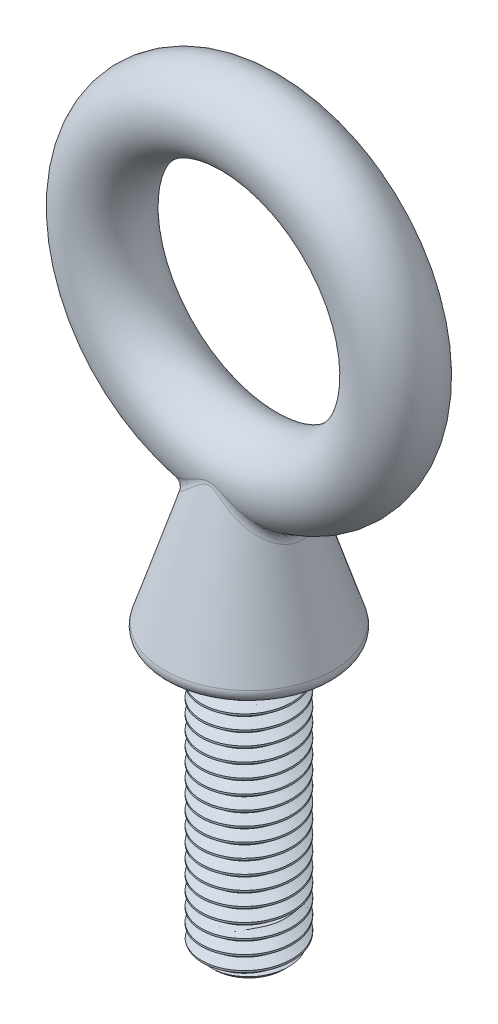
SolidWorks part; units mm, degrees
ref_plane "Front Plane" through (0, 0, 0) normal (0, 0, 1) x (1, 0, 0)
ref_plane "Top Plane" through (0, 0, 0) normal (0, 1, 0) x (1, 0, 0)
ref_plane "Right Plane" through (0, 0, 0) normal (1, 0, 0) x (0, 0, -1)
sketch "Sketch1" plane through (0, 0, 0) normal (0, 0, 1) x (1, 0, 0)
  line L0 (0, -26.1937) -> (0, -80.1688) construction
  line L1 (-6.35, -80.1688) -> (6.35, -80.1688) construction
  line L3 (0, -26.1937) -> (0, -15.0812) construction
  line L4 (-11.9062, -42.0687) -> (11.9063, -42.0687) construction
  circle A0 centre (0, 0) radius 26.1937 construction
  circle A1 centre (0, 20.6375) radius 5.5562 construction
  circle A2 centre (0, 0) radius 15.0813 construction
  point P7 (0, -26.1937)
  point P9 (0, -42.0687)
  point P10 (0, 26.1937)
  point P11 (0, 15.0812)
  point P14 (0, -80.1688)
  point P19 (0, -20.6375)
  point P21 (0, -42.0687)
sketch "Sketch2" plane through (0, 0, 0) normal (0, 1, 0) x (1, 0, 0)
  circle A0 centre (0, 0) radius 6.35
extrude "Boss-Extrude1" add sketch "Sketch2" against normal up to vertex (80.1688 mm away) from vertex at -42.0688 starting at point (0, -42.0687, 0)
sketch "Sketch3" plane through (0, -80.1688, 0) normal (0, -1, 0) x (1, 0, 0)
  circle A1 centre (0, 0) radius 6.35
  circle A2 centre (0, 0) radius 6.35
  point P0 (6.35, 0)
  point P1 (0, -6.35)
  dimension "D1" = 0
curve "Helix/Spiral1" pitch 1.9538 height 40.0538 turns 20.5 parameters "Pitch"=1.9538
sketch "Sketch4" plane through (0, 0, 0) normal (0, 0, 1) x (1, 0, 0)
  line L0 (6.5615, -80.0466) -> (6.5615, -82.0005) construction
  line L1 (6.5615, -82.0005) -> (4.8694, -81.0236) construction
  line L2 (4.8694, -81.0236) -> (6.5615, -80.0466) construction
  line L3 (5.0809, -80.9014) -> (5.0809, -81.1457) construction
  line L4 (6.35, -80.1688) -> (6.35, -81.8784) construction
  line L5 (4.8694, -81.0236) -> (5.0809, -81.0236) construction
  line L6 (6.35, -81.0236) -> (6.5615, -81.0236) construction
  line L7 (6.4558, -80.1077) -> (5.0809, -80.9014)
  line L8 (5.0809, -80.9014) -> (5.0809, -81.1457)
  line L9 (5.0809, -81.1457) -> (6.4558, -81.9394)
  line L10 (6.4558, -81.9394) -> (6.4558, -80.1077)
  point P13 (6.4558, -81.0236)
  dimension "D1" = 1.9538
  dimension "D2" = 0.2442
sweep "Cut-Sweep1" cut profiles "Sketch4" path "Helix/Spiral1" align with end faces yes
sketch "Sketch5" plane through (0, -80.1688, 0) normal (0, -1, 0) x (1, 0, 0)
  circle A0 centre (0, 0) radius 4.8694
extrude "Cut-Extrude1" cut sketch "Sketch5" against normal through all draft 45 flip side to cut
sketch "Sketch6" plane through (0, 0, 0) normal (1, 0, 0) x (0, 0, -1)
  circle A0 centre (0, 20.6375) radius 5.5563
ref_axis "Axis1" through (0, 0, -7.6398) along (0, 0, 1)
revolve "Revolve1" add sketch "Sketch6" angle 360 about axis through (0, 0, -7.6398) along (0, 0, 1)
sketch "Sketch7" plane through (0, -42.0687, 0) normal (0, 1, 0) x (1, 0, 0)
  circle A1 centre (0, 0) radius 6.35
  circle A2 centre (0, 0) radius 6.35
  dimension "D1" = 0
extrude "Boss-Extrude2" [suppressed] add sketch "Sketch7" along normal up to vertex (9.525 mm away)
sketch "Sketch8" plane through (0, 0, 0) normal (0, 0, 1) x (1, 0, 0)
  line L0 (0, -42.0687) -> (0, -20.6375)
  line L1 (0, -20.6375) -> (-5.5562, -20.6375)
  line L2 (-10.5172, -42.0687) -> (-11.9062, -42.0687) construction
  line L3 (-11.9062, -42.0687) -> (-11.9062, -40.6797) construction
  line L5 (-11.9062, -42.0687) -> (11.9063, -42.0687) construction
  line L6 (-11.84, -40.256) -> (-5.5562, -20.6375)
  line L9 (-10.5172, -42.0687) -> (0, -42.0687)
  arc A0 (-11.84, -40.256) -> (-10.5172, -42.0687) centre (-10.5172, -40.6797) ccw
  circle A1 centre (0, -20.6375) radius 5.5562 construction
  dimension "D1" = 1.3891
revolve "Revolve2" add sketch "Sketch8" angle 360 about L0
fillet "Fillet1" radius 1.3891 1 edges at (6.2964, -24.6961, 2.7135)
sketch "SketchX" plane through (0, 0, 0) normal (1, 0, 0) x (0, 0, -1)
  line L0 (6.35, -80.1688) -> (6.35, -54.2803) construction
  dimension "D1" = 25.8885
equation "\"D3@Helix/Spiral1\" = \"Pitch@Helix/Spiral1\" + \"Thread Lg.@Sketch1\""
equation "\"D1@Sketch4\" = \"Pitch@Helix/Spiral1\""
equation "\"D2@Sketch4\" = \"D1@Sketch4\" / 8"
equation "\"D1@Sketch8\" = \"A@Sketch1\" / 8"
equation "\"D1@Fillet1\" = \"A@Sketch1\" / 8"
equation "\"D1@SketchX\" = 1 + \"Pitch@Helix/Spiral1\" /  4"
